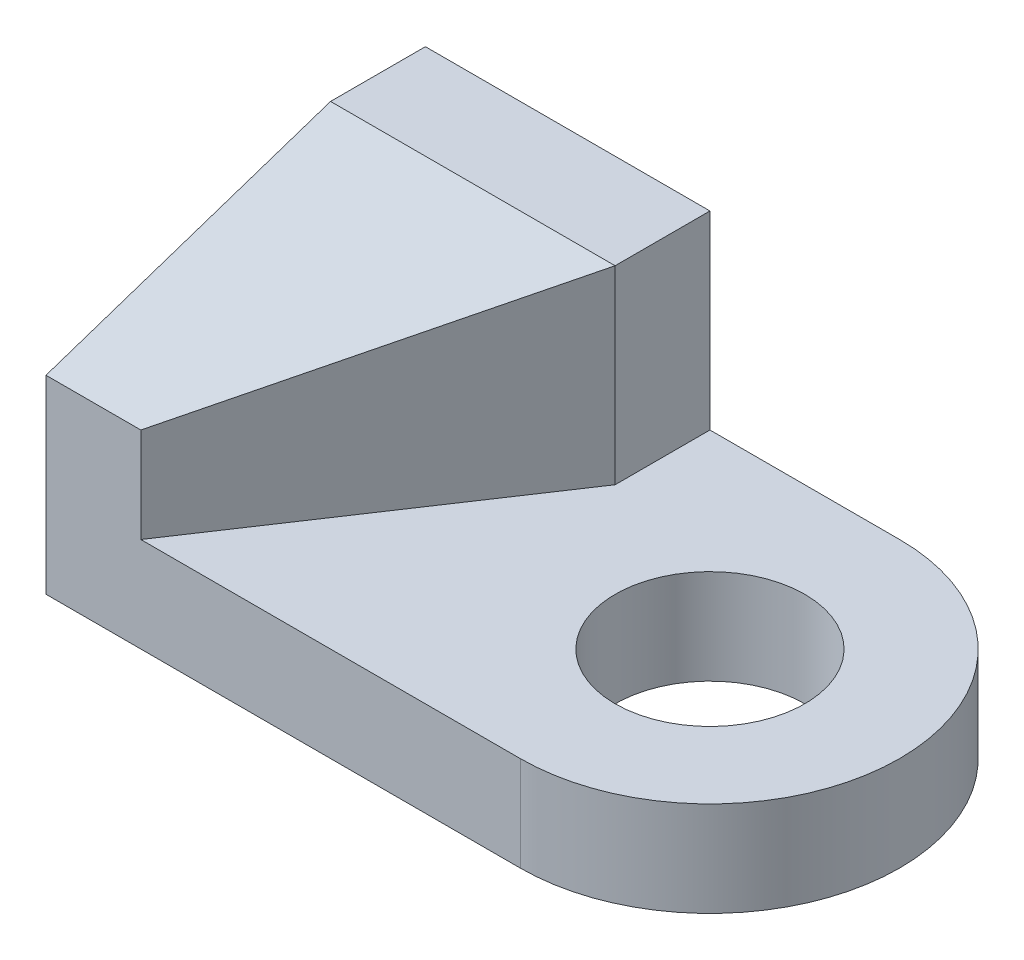
SolidWorks part; units mm, degrees
ref_plane "前基準面" through (0, 0, 0) normal (0, 0, 1) x (1, 0, 0)
ref_plane "上基準面" through (0, 0, 0) normal (0, 1, 0) x (1, 0, 0)
ref_plane "右基準面" through (0, 0, 0) normal (1, 0, 0) x (0, 0, -1)
sketch "草圖1" plane through (0, 0, 0) normal (0, 1, 0) x (1, 0, 0)
  line L0 (0, 10) -> (-25, 10)
  line L1 (-25, 10) -> (-25, -10)
  line L2 (-25, -10) -> (0, -10)
  line L3 (-25, 5) -> (-10, 5)
  line L4 (-25, 10) -> (-10, 10)
  line L5 (-25, 10) -> (-25, -10)
  line L6 (-25, -10) -> (-10, -10)
  line L7 (-10, 10) -> (-10, -10)
  circle A0 centre (0, 0) radius 5
  arc A1 (0, -10) -> (0, 10) centre (0, 0) ccw
  dimension "D1" = 10
  dimension "D2" = 20
  dimension "D3" = 25
  dimension "D4" = 15
  dimension "D5" = 5
extrude "填料-伸長1" add sketch "草圖1" along normal blind 5 contours L2 A1 L0 L7 A0 region at (9.7172, 0, 0)
extrude "填料-伸長2" add sketch "草圖1<3>" along normal blind 15 contours L7 L0 L1 L3 | L7 L3 L1 L2 region at (-17.5, 0, -7.5) region at (-17.5, 0, 2.5)
sketch "草圖1<3>" plane through (0, 0, 0) normal (0, 1, 0) x (1, 0, 0) same geometry as "草圖1"
sketch "草圖2" plane through (0, 15, 0) normal (0, 1, 0) x (1, 0, 0)
  line L0 (-25, 5) -> (-10, 5) construction
  line L1 (-25, 10) -> (-25, -10) construction
  line L2 (-10, 10) -> (-10, -10) construction
  line L3 (-10, 5) -> (-20, -10)
  line L4 (-25, -10) -> (-10, -10) construction
  line L5 (-10, 10) -> (-25, 10) construction
  line L6 (-20, -10) -> (-10, -10)
  line L7 (-10, -10) -> (-10, 5)
  dimension "D1" = 5
  dimension "D2" = 5
sketch "草圖3" plane through (-10, 0, 0) normal (1, 0, 0) x (0, 0, -1)
  line L0 (5, 15) -> (-10, 10)
  line L1 (5, 15) -> (-10, 15) construction
  line L2 (10, 15) -> (-10, 15) construction
  line L3 (-10, 15) -> (-10, 5) construction
  line L4 (-10, 10) -> (-10, 15)
  line L5 (-10, 15) -> (5, 15)
  dimension "D1" = 5
extrude "除料-伸長1" cut sketch "草圖3" against normal blind 15
extrude "除料-伸長2" cut sketch "草圖2" against normal blind 10
